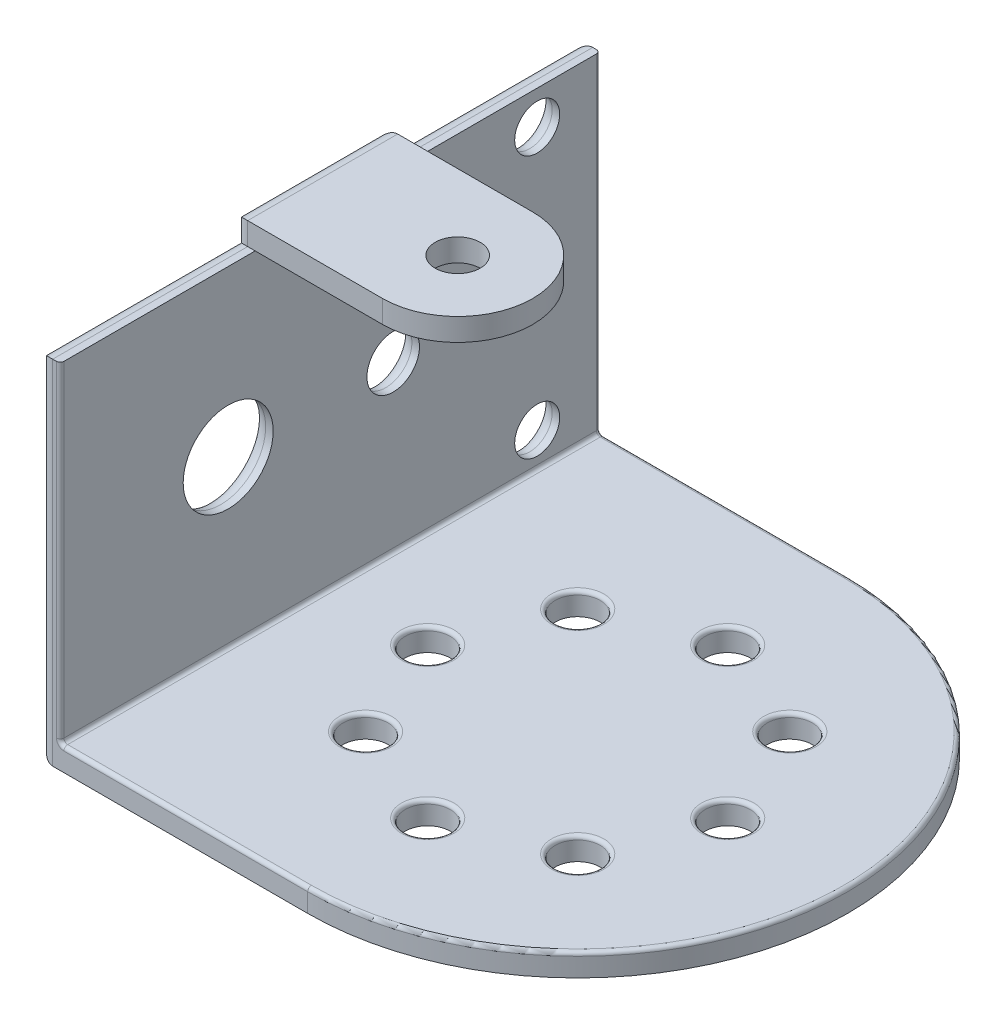
SolidWorks part; units mm, degrees
material "PLA"
ref_plane "Alzado" through (0, 0, 0) normal (0, 0, 1) x (1, 0, 0)
ref_plane "Planta" through (0, 0, 0) normal (0, 1, 0) x (1, 0, 0)
ref_plane "Vista lateral" through (0, 0, 0) normal (1, 0, 0) x (0, 0, -1)
sketch "Croquis1" plane through (0, 0, 0) normal (1, 0, 0) x (0, 0, -1)
  line L0 (18, 0) -> (-18, 0) construction
  line L1 (-18, -11) -> (18, -11)
  line L2 (-18, -11) -> (-18, 11)
  line L3 (-18, 11) -> (18, 11)
  line L4 (18, -11) -> (18, 11)
  line L5 (-18, -11) -> (18, 11) construction
  line L6 (-18, 11) -> (18, -11) construction
  circle A0 centre (13.8, 8.75) radius 1.5
  circle A1 centre (-6.8, 0) radius 3
  circle A2 centre (13.8, -8.75) radius 1.5
  circle A3 centre (4.2, 0) radius 1.75
  point P0 (0, 0)
  dimension "D3" = 4.2
  dimension "D5" = 3
  dimension "D6" = 6
  dimension "D8" = 13.8
  dimension "D9" = 3.5
  dimension "D1" = 22
  dimension "D2" = 36
  dimension "D4" = 2.25
  dimension "D7" = 11.2
extrude "Saliente-Extruir1" add sketch "Croquis1" along normal blind 1.5
sketch "Croquis3" plane through (0, -11, 0) normal (0, -1, 0) x (1, 0, 0)
  line L0 (0, 18) -> (0, -18) construction
  line L1 (18, -18) -> (0, -18)
  line L2 (18, 18) -> (0, 18)
  line L3 (0, 18) -> (0, -18)
  arc A0 (18, -18) -> (18, 18) centre (18, 0) ccw
  point P1 (0, 0)
  point P8 (0, 26.3991)
  dimension "D1" = 36
  dimension "D2" = 18
extrude "Extruir-Lámina1" [suppressed] add sketch "Croquis3" along normal blind 1.5 separate body thin thin type one direction wall 10
extrude "Saliente-Extruir3" add sketch "Croquis3<2>" along normal blind 1.5
sketch "Croquis3<2>" plane through (0, -11, 0) normal (0, -1, 0) x (1, 0, 0) same geometry as "Croquis3"
sketch "Croquis4" plane through (0, 11, 0) normal (0, 1, 0) x (1, 0, 0)
  line L0 (10, 5) -> (0, 5)
  line L1 (0, 18) -> (0, -18) construction
  line L2 (10, -5) -> (0, -5)
  line L7 (0, 18) -> (0, -18)
  line L8 (0, -18) -> (1.5, -18)
  line L9 (1.5, -18) -> (1.5, 18)
  line L10 (1.5, 18) -> (0, 18)
  line L11 (0, 5) -> (0, -5)
  arc A0 (10, -5) -> (10, 5) centre (10, 0) ccw
  point P1 (10, 2.2607)
  point P8 (0, 0)
  dimension "D1" = 10
  dimension "D2" = 10
  dimension "D3" = 0
extrude "Saliente-Extruir4" add sketch "Croquis4" along normal blind 1.5
sketch "Croquis5" plane through (0, 12.5, 0) normal (0, 1, 0) x (1, 0, 0)
  circle A0 centre (10, 0) radius 1.5
  dimension "D1" = 3
extrude "Cortar-Extruir1" cut sketch "Croquis5" against normal up to next
sketch "Croquis7" plane through (0, -12.5, 0) normal (0, -1, 0) x (1, 0, 0)
  line L0 (18, 0) -> (36, 0) construction
  arc A0 (18, -18) -> (18, 18) centre (18, 0) ccw construction
  circle A1 centre (28, 0) radius 1.5
  circle A2 centre (25.0711, -7.0711) radius 1.5
  circle A3 centre (18, -10) radius 1.5
  circle A4 centre (10.9289, -7.0711) radius 1.5
  circle A5 centre (8, 0) radius 1.5
  circle A6 centre (10.9289, 7.0711) radius 1.5
  circle A7 centre (18, 10) radius 1.5
  circle A8 centre (25.0711, 7.0711) radius 1.5
  point P8 (18, 0)
  point P25 (18, 0)
  dimension "D1" = 3
  dimension "D2" = 10
  dimension "D4" = 28
  dimension "D3" = 8
extrude "Cortar-Extruir2" cut sketch "Croquis7" against normal up to next
fillet "Redondeo1" [suppressed] radius 1
fillet "Redondeo2" radius 1 12 edges at (0, 0, -5.95) (0, 0, 3.8) (0, 11, -11.5) (0, 11.75, -5) (0, 12.5, 0) (0, 11.75, 5) (0, 11, 11.5) (0, -0.75, 18) (0, -12.5, 0) (0, -0.75, -18) (0, 8.75, -15.3) (0, -8.75, -12.3)
fillet "Redondeo3" radius 0.25 14 edges at (1.5, 0, -18) (1.5, 0, 18) (9.75, -11, -18) (36, -11, 0) (9.75, -11, 18) (1.5, -11, 0) (28, -11, -1.5) (25.0711, -11, -8.5711) (18, -11, -11.5) (10.9289, -11, -8.5711) (8, -11, -1.5) (10.9289, -11, 5.5711) (18, -11, 8.5) (25.0711, -11, 5.5711)
